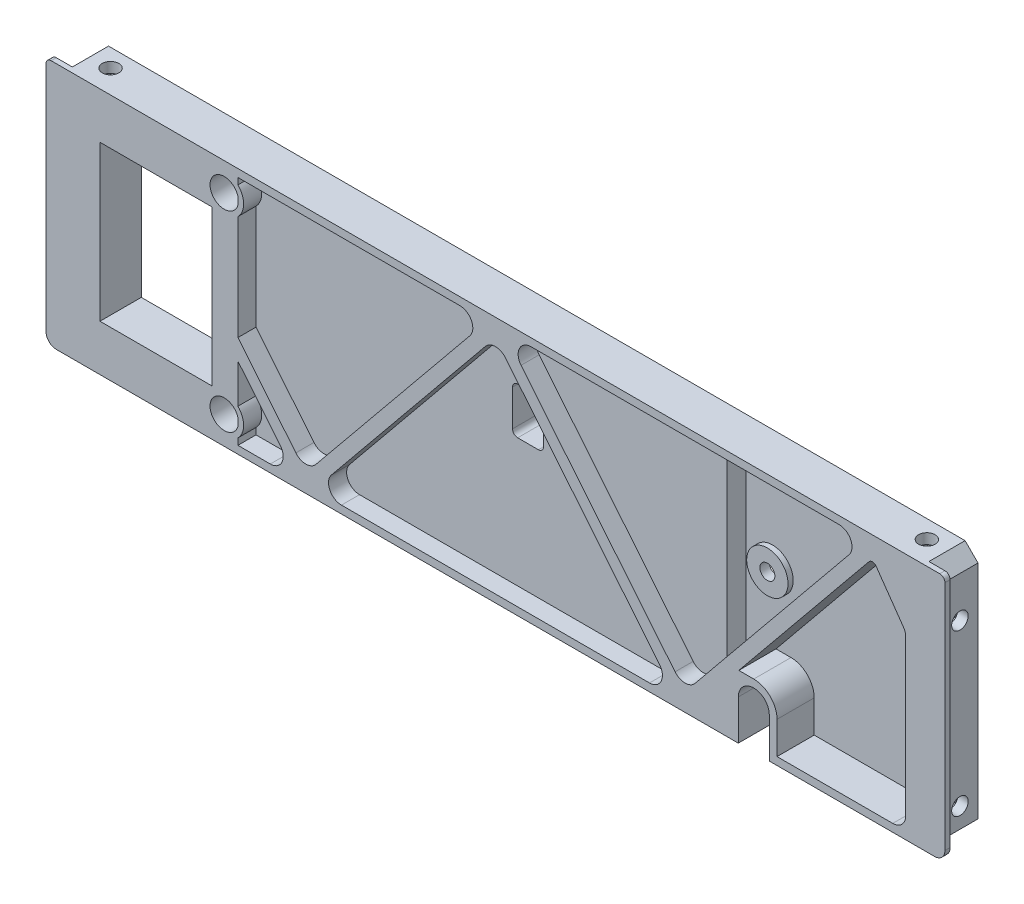
SolidWorks part; units mm, degrees
ref_plane "Front Plane" through (0, 0, 0) normal (0, 0, 1) x (1, 0, 0)
ref_plane "Top Plane" through (0, 0, 0) normal (0, 1, 0) x (1, 0, 0)
ref_plane "Right Plane" through (0, 0, 0) normal (1, 0, 0) x (0, 0, -1)
sketch "Sketch1" plane through (0, 0, 0) normal (0, 0, 1) x (1, 0, 0)
  line L1 (87, -25.55) -> (-87, -25.55)
  line L2 (87, -25.55) -> (87, 25.55)
  line L3 (87, 25.55) -> (-87, 25.55)
  line L4 (-87, -25.55) -> (-87, 25.55)
  line L5 (87, -25.55) -> (-87, 25.55) construction
  line L6 (87, 25.55) -> (-87, -25.55) construction
  point P0 (0, 0)
  dimension "D1" = 174
  dimension "D2" = 51.1
extrude "Boss-Extrude1" add sketch "Sketch1" against normal blind 8
sketch "Sketch2" plane through (0, 0, -8) normal (0, 0, -1) x (-1, 0, 0)
  line L5 (-87, -25.55) -> (-87, 25.55) construction
  line L6 (-87, 25.55) -> (87, 25.55) construction
  line L13 (85.4, -23.95) -> (85.4, 23.95)
  line L14 (-85.4, -23.95) -> (85.4, -23.95)
  line L15 (-85.4, 23.95) -> (-85.4, -23.95)
  line L16 (85.4, 23.95) -> (-85.4, 23.95)
  point P2 (0, 23.95)
  point P5 (85.4, 0)
  dimension "D1" = 1.6
  dimension "D2" = 1.6
extrude "Cut-Extrude1" cut sketch "Sketch2" against normal offset from surface (7 mm away) 1 flip side to cut up to face at (0, 0, 0)
chamfer "Chamfer1" distance 2.5 angle 45 4 edges at (-85.4, -23.95, -4.5) (-85.4, 23.95, -4.5) (85.4, -23.95, -4.5) (85.4, 23.95, -4.5)
fillet "Fillet1" radius 0.5 2 edges at (-87, 25.55, -0.5) (87, 25.55, -0.5)
sketch "Sketch3" plane through (0, 0, 0) normal (0, 0, 1) x (1, 0, 0)
  line L1 (-82.9, 23.95) -> (-85.4, 21.45) construction
  line L2 (-82.9, 23.95) -> (82.9, 23.95) construction
  line L3 (-82.9, 23.95) -> (-85.4, 21.45) construction
  line L4 (-82.9, 23.95) -> (82.9, 23.95) construction
  line L5 (85.4, 21.45) -> (82.9, 23.95) construction
  line L6 (85.4, 21.45) -> (85.4, -21.45) construction
  line L7 (82.9, -23.95) -> (85.4, -21.45) construction
  line L8 (82.9, -23.95) -> (-82.9, -23.95) construction
  line L9 (-85.4, -21.45) -> (-82.9, -23.95) construction
  line L10 (-85.4, -21.45) -> (-85.4, 21.45) construction
  line L11 (85.4, 21.45) -> (82.9, 23.95) construction
  line L12 (85.4, 21.45) -> (85.4, -21.45) construction
  line L13 (82.9, -23.95) -> (85.4, -21.45) construction
  line L14 (82.9, -23.95) -> (-82.9, -23.95) construction
  line L15 (-85.4, -21.45) -> (-82.9, -23.95) construction
  line L16 (-85.4, -21.45) -> (-85.4, 21.45) construction
  line L26 (79.4, -22.45) -> (-79.4, -22.45)
  line L27 (79.4, -22.45) -> (79.4, 22.45)
  line L28 (79.4, 22.45) -> (-79.4, 22.45)
  line L29 (-79.4, -22.45) -> (-79.4, 22.45)
  line L30 (79.4, -22.45) -> (-79.4, 22.45) construction
  line L31 (79.4, 22.45) -> (-79.4, -22.45) construction
  point P4 (0, 0)
  dimension "D1" = 3
  dimension "D2" = 6
extrude "Cut-Extrude2" cut sketch "Sketch3" against normal offset from surface (7.2 mm away) 0.8 up to face at (0, 0, -8)
sketch "Sketch9" plane through (0, 0, 0) normal (0, 0, 1) x (1, 0, 0)
  line L0 (-73.4, 22.45) -> (-73.4, 19.45)
  line L1 (-79.4, 22.45) -> (79.4, 22.45) construction
  line L2 (-73.4, 19.45) -> (-79.4, 10.8811)
  line L3 (-79.4, -22.45) -> (-79.4, 22.45) construction
  line L4 (-79.4, 10.8811) -> (-79.4, 22.45)
  line L5 (-79.4, 22.45) -> (-73.4, 22.45)
  dimension "D1" = 6
  dimension "D2" = 35
  dimension "D3" = 3
extrude "Boss-Extrude2" add sketch "Sketch9" against normal up to surface (7.2 mm away) up to face at (0, 0, -7.2)
hole_wizard "Ø3.0mm Dowel Hole1" positions "Sketch4" profile "Sketch5" hole size "Ø3.0" standard "ANSI Metric"
sketch "Sketch4" plane through (-85.4, 0, 0) normal (-1, 0, 0) x (0, 0, 1)
  line L0 (-4.5, 13.55) -> (-4.5, -17.55) construction
  line L2 (-8, -21.45) -> (-8, 21.45) construction
  line L3 (-1, 25.55) -> (0, 25.55) construction
  line L5 (-1, -25.55) -> (0, -25.55) construction
  point P0 (-4.5, 13.55)
  point P3 (-4.5, -17.55)
  point P15 (-0.5, 25.55)
  dimension "D1" = 3.5
  dimension "D2" = 12
  dimension "D3" = 8
sketch "Sketch5" plane through (-85.4, 13.55, -4.5) normal (0, 1, 0) x (0, 0, 1)
  line L0 (0, 0) -> (0, 5)
  line L1 (0, 5) -> (1.6, 5)
  line L2 (1.6, 5) -> (1.6, 0)
  line L5 (1.6, 0) -> (0, 0)
  line L10 (0, 5) -> (-1.6, 5) construction
  line L11 (0, -6.35) -> (0, 107.95) construction
  dimension "Hole Dia." = 3.2
  dimension "Hole Depth" = 5
  dimension "Drill Angle" = 180
hole_wizard "Ø3.0mm Dowel Hole2" positions "Sketch7" profile "Sketch8" hole size "Ø3.0" standard "ANSI Metric"
sketch "Sketch7" plane through (0, 23.95, 0) normal (0, 1, 0) x (1, 0, 0)
  line L0 (-82.9, 8) -> (82.9, 8) construction
  line L1 (-87, 0) -> (-87, 1) construction
  point P0 (-79, 4.5)
  dimension "D1" = 3.5
  dimension "D2" = 8
sketch "Sketch8" plane through (-79, 23.95, -4.5) normal (1, 0, 0) x (0, 0, 1)
  line L0 (0, 0) -> (0, 5)
  line L1 (0, 5) -> (1.6, 5)
  line L2 (1.6, 5) -> (1.6, 0)
  line L5 (1.6, 0) -> (0, 0)
  line L10 (0, 5) -> (-1.6, 5) construction
  line L11 (0, -6.35) -> (0, 107.95) construction
  dimension "Hole Dia." = 3.2
  dimension "Hole Depth" = 5
  dimension "Drill Angle" = 180
sketch "Sketch10" plane through (-85.4, 0, 0) normal (-1, 0, 0) x (0, 0, 1)
  line L0 (-8, -21.45) -> (-8, 21.45) construction
  line L1 (-8, 16.3) -> (-1.75, 16.3)
  line L2 (-8, 16.3) -> (-8, 10.8)
  line L3 (-8, 10.8) -> (-1.75, 10.8)
  line L4 (-1.75, 16.3) -> (-1.75, 10.8)
  line L6 (-8, -14.8) -> (-1.75, -14.8)
  line L7 (-8, -14.8) -> (-8, -20.3)
  line L8 (-8, -20.3) -> (-1.75, -20.3)
  line L9 (-1.75, -14.8) -> (-1.75, -20.3)
  point P6 (-1.75, -17.55)
  point P8 (-1.75, 13.55)
  dimension "D1" = 5.5
  dimension "D2" = 2.75
extrude "Cut-Extrude3" cut sketch "Sketch10" against normal blind 1.8 from offset 2 offset against normal yes
sketch "Sketch11" plane through (0, 23.95, 0) normal (0, 1, 0) x (1, 0, 0)
  line L0 (-82.9, 8) -> (82.9, 8) construction
  line L1 (-81.75, 8) -> (-76.25, 8)
  line L2 (-81.75, 8) -> (-81.75, 1.75)
  line L3 (-81.75, 1.75) -> (-76.25, 1.75)
  line L4 (-76.25, 8) -> (-76.25, 1.75)
  point P6 (-79, 1.75)
  dimension "D1" = 5.5
  dimension "D2" = 2.75
extrude "Cut-Extrude4" cut sketch "Sketch11" against normal blind 1.8 from offset 2 offset against normal yes
mirror "Mirror1" about plane through (0, 0, 0) normal (1, 0, 0) of "Cut-Extrude4", "Cut-Extrude3", "Ø3.0mm Dowel Hole2", "Ø3.0mm Dowel Hole1", "Boss-Extrude2"
sketch "Sketch12" plane through (0, 0, -7.2) normal (0, 0, 1) x (1, 0, 0)
  line L0 (-73.4, 22.45) -> (-36.7, -22.45) construction
  line L1 (-79.4, -22.45) -> (79.4, -22.45) construction
  line L2 (-36.7, -22.45) -> (0, 22.45) construction
  line L3 (73.4, 22.45) -> (-73.4, 22.45) construction
  line L4 (0, 22.45) -> (36.7, -22.45) construction
  line L5 (36.7, -22.45) -> (73.4, 22.45) construction
  line L6 (-74.3678, 21.6589) -> (-37.4743, -23.4779)
  line L7 (-35.9257, -23.4779) -> (0, 20.4748)
  line L8 (0, 20.4748) -> (35.9257, -23.4779)
  line L9 (37.4743, -23.4779) -> (74.3678, 21.6589)
  line L10 (-72.4322, 23.2411) -> (-36.7, -20.4748)
  line L11 (-36.7, -20.4748) -> (-0.7743, 23.4779)
  line L12 (0.7743, 23.4779) -> (36.7, -20.4748)
  line L13 (36.7, -20.4748) -> (72.4322, 23.2411)
  line L14 (0, 20.4748) -> (36.7, -24.4252) construction
  line L15 (36.7, -24.4252) -> (74.3678, 21.6589) construction
  line L16 (-36.7, -20.4748) -> (0, 24.4252) construction
  line L17 (0, 24.4252) -> (36.7, -20.4748) construction
  line L18 (-74.3678, 21.6589) -> (-36.7, -24.4252) construction
  line L19 (-36.7, -24.4252) -> (0, 20.4748) construction
  arc A0 (-74.3678, 21.6589) -> (-72.4322, 23.2411) centre (-73.4, 22.45) cw
  arc A1 (74.3678, 21.6589) -> (72.4322, 23.2411) centre (73.4, 22.45) ccw
  arc A2 (35.9257, -23.4779) -> (37.4743, -23.4779) centre (36.7, -22.845) ccw
  arc A3 (-0.7743, 23.4779) -> (0.7743, 23.4779) centre (0, 22.845) cw
  arc A4 (-37.4743, -23.4779) -> (-35.9257, -23.4779) centre (-36.7, -22.845) ccw
  dimension "D3" = 1
  dimension "D1" = 1.25
extrude "Boss-Extrude3" add sketch "Sketch12" along normal up to surface (7.2 mm away) up to face at (0, 7.5828, 0)
sketch "Sketch13" plane through (0, 0, 0) normal (0, 0, 1) x (1, 0, 0)
  line L0 (-73.4, 19.45) -> (-73.4, 20.4748)
  line L1 (-73.4, 20.4748) -> (-72.5623, 19.45)
  line L2 (-73.4, 20.4748) -> (-38.3144, -22.45) construction
  line L3 (-72.5623, 19.45) -> (-73.4, 19.45)
  line L4 (0, 0) -> (0, 25.4565) construction
  line L5 (72.5623, 19.45) -> (73.4, 19.45)
  line L6 (73.4, 20.4748) -> (72.5623, 19.45)
  line L7 (73.4, 19.45) -> (73.4, 20.4748)
extrude "Small Fix" add sketch "Sketch13" against normal up to surface (7.2 mm away) up to face at (-68.7829, 1.1812, -7.2)
sketch "Sketch14" plane through (0, 0, -1) normal (0, 0, -1) x (-1, 0, 0)
  line L0 (87, -25.55) -> (87, 25.05) construction
  line L1 (-87, -25.55) -> (87, -25.55)
  line L2 (-87, -25.55) -> (-87, -23.95)
  line L3 (-87, -23.95) -> (87, -23.95)
  line L4 (87, -25.55) -> (87, -23.95)
  line L5 (-82.9, -23.95) -> (82.9, -23.95) construction
extrude "Cut-Extrude5" cut sketch "Sketch14" against normal through all
fillet "Fillet2" radius 2.5 15 edges at (79.4, -22.45, -3.6) (79.4, 10.8811, -3.6) (38.3144, -22.45, -3.6) (71.7856, 22.45, -3.6) (36.7, -20.4748, -3.6) (1.6144, 22.45, -3.6) (35.0856, -22.45, -3.6) (0, 20.4748, -3.6) (-35.0856, -22.45, -3.6) (-1.6144, 22.45, -3.6) (-36.7, -20.4748, -3.6) (-71.7856, 22.45, -3.6) (-79.4, 10.8811, -3.6) (-79.4, -22.45, -3.6) (-38.3144, -22.45, -3.6)
fillet "Fillet3" radius 1 4 edges at (73.4, 19.45, -3.6) (72.5623, 19.45, -3.6) (-72.5623, 19.45, -3.6) (-73.4, 19.45, -3.6)
fillet "Fillet4" radius 2 2 edges at (-87, -23.95, -0.5) (87, -23.95, -0.5)
sketch "Sketch23" plane through (0, 0, -1) normal (0, 0, -1) x (-1, 0, 0)
  line L0 (82.9, 23.95) -> (-82.9, 23.95) construction
  line L1 (-87, 25.55) -> (87, 25.55)
  line L2 (-87, 25.55) -> (-87, 23.95)
  line L3 (-87, 23.95) -> (87, 23.95)
  line L4 (87, 25.55) -> (87, 23.95)
  line L5 (87, -21.95) -> (87, 25.05) construction
  line L6 (86.5, 25.55) -> (-86.5, 25.55) construction
  line L7 (-87, 25.05) -> (-87, -21.95) construction
extrude "Cut-Extrude9" cut sketch "Sketch23" against normal through all
sketch "Sketch24" plane through (0, 0, 0) normal (0, 0, 1) x (1, 0, 0)
  line L0 (79.4, -19.95) -> (79.4, 10.0929) construction
  line L1 (49.85, 22.45) -> (73.6986, 22.45) construction
  line L2 (49.85, 22.45) -> (49.85, -22.45) construction
  line L3 (49.85, -22.45) -> (79.4, -22.45) construction
  line L4 (79.4, 10.0929) -> (79.4, -22.45) construction
  line L5 (43.5867, -22.45) -> (76.9, -22.45) construction
  line L6 (66.5133, 22.45) -> (6.8867, 22.45) construction
  line L7 (78.9479, 11.5268) -> (73.6986, 19.0236) construction
  line L8 (78.9479, 11.5268) -> (73.6986, 19.0236) construction
  line L9 (73.6986, 19.0236) -> (73.6986, 22.45) construction
  line L10 (0, 23.95) -> (0, -23.95) construction
  line L11 (54.85, 15) -> (76.55, 15) construction
  line L12 (54.85, 15) -> (54.85, -15) construction
  line L13 (54.85, -15) -> (76.55, -15) construction
  line L14 (76.55, 15) -> (76.55, -15) construction
  line L15 (87, 23.95) -> (-87, 23.95) construction
  line L16 (-85, -23.95) -> (85, -23.95) construction
  line L17 (-76.55, 15) -> (-76.55, -15) construction
  line L18 (-54.85, -15) -> (-76.55, -15) construction
  line L19 (-54.85, 15) -> (-54.85, -15) construction
  line L20 (-54.85, 15) -> (-76.55, 15) construction
  line L21 (-73.6986, 19.0236) -> (-73.6986, 22.45)
  line L22 (-78.9479, 11.5268) -> (-73.6986, 19.0236)
  line L23 (-79.4, 10.0929) -> (-79.4, -22.45)
  line L24 (-49.85, -22.45) -> (-79.4, -22.45)
  line L25 (-49.85, 22.45) -> (-49.85, -22.45)
  line L26 (-49.85, 22.45) -> (-73.6986, 22.45)
  line L27 (87, -21.95) -> (87, 23.95) construction
  arc A0 (79.4, 10.0929) -> (78.9479, 11.5268) centre (76.9, 10.0929) ccw construction
  arc A1 (79.4, 10.0929) -> (78.9479, 11.5268) centre (76.9, 10.0929) ccw construction
  arc A2 (-79.4, 10.0929) -> (-78.9479, 11.5268) centre (-76.9, 10.0929) cw
  point P18 (0, 0)
  point P21 (76.55, 0)
  dimension "D1" = 10.45
  dimension "D2" = 21.7
  dimension "D3" = 30
  dimension "D4" = 5
extrude "Boss-Extrude7" add sketch "Sketch24" against normal up to surface (7.2 mm away) up to face at (36.7, 7.6215, -7.2)
sketch "Sketch26" plane through (0, 0, 0) normal (0, 0, 1) x (1, 0, 0)
  line L8 (-54.85, 15) -> (-54.85, -15) construction
  line L9 (-54.85, -15) -> (-76.55, -15) construction
  line L10 (-76.55, 15) -> (-76.55, -15) construction
  line L11 (-54.85, 15) -> (-76.55, 15) construction
  line L12 (-54.85, 15) -> (-54.85, -15)
  line L13 (-54.85, -15) -> (-76.55, -15)
  line L14 (-76.55, 15) -> (-76.55, -15)
  line L15 (-54.85, 15) -> (-76.55, 15)
extrude "Cut-Extrude10" cut sketch "Sketch26" against normal up to surface (8 mm away) up to face at (82.5, 13.55, -8)
sketch "Sketch27" plane through (0, 0, -8) normal (0, 0, -1) x (-1, 0, 0)
  line L0 (82.9, 23.95) -> (-82.9, 23.95) construction
  line L1 (2.75, 21.95) -> (45.85, 21.95) construction
  line L2 (2.75, 21.95) -> (2.75, 4.65) construction
  line L3 (2.75, 4.65) -> (45.85, 4.65) construction
  line L4 (45.85, 21.95) -> (45.85, 4.65) construction
  line L5 (18.72, -1.95) -> (45.85, -1.95) construction
  line L6 (18.72, -1.95) -> (18.72, -21.95) construction
  line L7 (18.72, -21.95) -> (45.85, -21.95) construction
  line L8 (45.85, -1.95) -> (45.85, -21.95) construction
  line L9 (-40.45, 21.95) -> (-7.75, 21.95) construction
  line L10 (-40.45, 21.95) -> (-40.45, 4.23) construction
  line L11 (-40.45, 4.23) -> (-7.75, 4.23) construction
  line L12 (-7.75, 21.95) -> (-7.75, 4.23) construction
  line L13 (-82.9, -23.95) -> (82.9, -23.95) construction
  line L15 (54.85, 15) -> (54.85, -15) construction
  line L24 (-40.28, -1.45) -> (4.72, -1.45) construction
  line L25 (-40.28, -1.45) -> (-40.28, -21.95) construction
  line L26 (-40.28, -21.95) -> (4.72, -21.95) construction
  line L27 (4.72, -1.45) -> (4.72, -21.95) construction
  dimension "D1" = 43.1
  dimension "D2" = 17.3
  dimension "D3" = 27.13
  dimension "D4" = 20
  dimension "D5" = 32.7
  dimension "D6" = 17.72
  dimension "D7" = 2
  dimension "D8" = 20.5
  dimension "D9" = 45
  dimension "D10" = 2
  dimension "D11" = 14
  dimension "D12" = 9
  dimension "D13" = 10.5
fillet "Fillet5" radius 1 2 edges at (87, 23.95, -0.5) (-87, 23.95, -0.5)
sketch "Sketch28" plane through (0, 0, -7.2) normal (0, 0, 1) x (1, 0, 0)
  line L0 (43.5867, -22.45) -> (76.9, -22.45) construction
  line L1 (-49.85, 22.45) -> (41.28, 22.45)
  line L2 (-49.85, 22.45) -> (-49.85, -22.45)
  line L3 (-49.85, -22.45) -> (41.28, -22.45)
  line L4 (41.28, 22.45) -> (41.28, -22.45)
  line L5 (40.28, -1.45) -> (40.28, -21.95) construction
  dimension "D1" = 1
extrude "Boss-Extrude8" add sketch "Sketch28" along normal blind 3.7
sketch "Sketch29" plane through (0, 0, -8) normal (0, 0, -1) x (-1, 0, 0)
  line L0 (-7.75, 21.95) -> (-7.75, 4.23) construction
  line L1 (-40.45, 4.23) -> (-7.75, 4.23) construction
  line L2 (-40.45, 21.95) -> (-40.45, 4.23) construction
  line L3 (-40.45, 21.95) -> (-7.75, 21.95) construction
  line L4 (-7.75, 21.95) -> (-7.75, 4.23) construction
  line L5 (-40.45, 4.23) -> (-7.75, 4.23) construction
  line L6 (-40.45, 21.95) -> (-40.45, 4.23) construction
  line L7 (-40.45, 21.95) -> (-7.75, 21.95) construction
  line L8 (4.72, -1.45) -> (4.72, -21.95) construction
  line L9 (-40.28, -21.95) -> (4.72, -21.95) construction
  line L10 (-40.28, -1.45) -> (-40.28, -21.95) construction
  line L11 (-40.28, -1.45) -> (4.72, -1.45) construction
  line L12 (18.72, -1.95) -> (18.72, -21.95) construction
  line L13 (18.72, -21.95) -> (45.85, -21.95) construction
  line L14 (45.85, -1.95) -> (45.85, -21.95) construction
  line L15 (18.72, -1.95) -> (45.85, -1.95) construction
  line L16 (2.75, 4.65) -> (45.85, 4.65) construction
  line L17 (45.85, 21.95) -> (45.85, 4.65) construction
  line L18 (2.75, 21.95) -> (45.85, 21.95) construction
  line L19 (2.75, 21.95) -> (2.75, 4.65) construction
  line L20 (4.72, -1.45) -> (4.72, -21.95) construction
  line L21 (-40.28, -21.95) -> (4.72, -21.95) construction
  line L22 (-40.28, -1.45) -> (-40.28, -21.95) construction
  line L23 (-40.28, -1.45) -> (4.72, -1.45) construction
  line L24 (18.72, -1.95) -> (18.72, -21.95) construction
  line L25 (18.72, -21.95) -> (45.85, -21.95) construction
  line L26 (45.85, -1.95) -> (45.85, -21.95) construction
  line L27 (18.72, -1.95) -> (45.85, -1.95) construction
  line L28 (2.75, 4.65) -> (45.85, 4.65) construction
  line L29 (45.85, 21.95) -> (45.85, 4.65) construction
  line L30 (2.75, 21.95) -> (45.85, 21.95) construction
  line L31 (2.75, 21.95) -> (2.75, 4.65) construction
  line L32 (-7.6, 22.1) -> (-7.6, 4.08)
  line L33 (-40.6, 4.08) -> (-7.6, 4.08)
  line L34 (-40.6, 22.1) -> (-40.6, 4.08)
  line L35 (-40.6, 22.1) -> (-7.6, 22.1)
  line L36 (4.87, -1.3) -> (4.87, -22.1)
  line L37 (-40.43, -22.1) -> (4.87, -22.1)
  line L38 (-40.43, -1.3) -> (-40.43, -22.1)
  line L39 (-40.43, -1.3) -> (4.87, -1.3)
  line L40 (18.57, -1.8) -> (18.57, -22.1)
  line L41 (18.57, -22.1) -> (46, -22.1)
  line L42 (46, -1.8) -> (46, -22.1)
  line L43 (18.57, -1.8) -> (46, -1.8)
  line L44 (2.6, 4.5) -> (46, 4.5)
  line L45 (46, 22.1) -> (46, 4.5)
  line L46 (2.6, 22.1) -> (46, 22.1)
  line L47 (2.6, 22.1) -> (2.6, 4.5)
  dimension "D1" = 0.15
extrude "Cut-Extrude11" cut sketch "Sketch29" against normal blind 1.6
sketch "Sketch30" plane through (0, 0, -6.4) normal (0, 0, -1) x (-1, 0, 0)
  line L0 (4.87, -1.3) -> (-40.43, -1.3) construction
  line L1 (-40.43, -1.3) -> (-26.43, -1.3)
  line L2 (-40.43, -1.3) -> (-40.43, -11.7)
  line L3 (-40.43, -11.7) -> (-26.43, -11.7)
  line L4 (-26.43, -1.3) -> (-26.43, -11.7)
  line L7 (-40.43, -1.3) -> (-40.43, -22.1) construction
  line L8 (-40.43, -22.1) -> (4.87, -22.1) construction
  line L9 (3.67, -1.3) -> (-3.13, -1.3)
  line L10 (3.67, -1.3) -> (3.67, -22.1)
  line L11 (3.67, -22.1) -> (-3.13, -22.1)
  line L12 (-3.13, -1.3) -> (-3.13, -22.1)
  line L13 (4.87, -22.1) -> (4.87, -1.3) construction
  line L14 (4.87, -22.1) -> (4.87, -1.3) construction
  line L15 (46, 22.1) -> (2.6, 22.1) construction
  line L16 (5.6, 22.1) -> (34, 22.1)
  line L17 (5.6, 22.1) -> (5.6, 4.5)
  line L18 (5.6, 4.5) -> (34, 4.5)
  line L19 (34, 22.1) -> (34, 4.5)
  line L20 (2.6, 4.5) -> (46, 4.5) construction
  line L21 (46, 22.1) -> (2.6, 22.1) construction
  line L22 (46, 4.5) -> (39, 4.5)
  line L23 (46, 4.5) -> (46, 22.1)
  line L24 (46, 22.1) -> (39, 22.1)
  line L25 (39, 4.5) -> (39, 22.1)
  line L26 (2.6, 22.1) -> (2.6, 4.5) construction
  line L27 (46, -1.8) -> (18.57, -1.8) construction
  line L29 (22.57, -1.8) -> (22.57, -22.1)
  line L31 (39.5, -1.8) -> (39.5, -22.1)
  line L32 (18.57, -22.1) -> (46, -22.1) construction
  line L33 (18.57, -1.8) -> (18.57, -22.1) construction
  line L34 (46, -22.1) -> (46, -1.8) construction
  line L36 (22.57, -1.8) -> (18.57, -1.8)
  line L37 (18.57, -1.8) -> (18.57, -22.1)
  line L38 (18.57, -22.1) -> (22.57, -22.1)
  line L39 (39.5, -22.1) -> (46, -22.1)
  line L40 (46, -22.1) -> (46, -1.8)
  line L41 (46, -1.8) -> (39.5, -1.8)
  point P11 (-40.43, -11.7)
  dimension "D1" = 14
  dimension "D2" = 1.2
  dimension "D3" = 8
  dimension "D4" = 7
  dimension "D5" = 12
  dimension "D6" = 3
  dimension "D7" = 4
  dimension "D8" = 6.5
extrude "Cut-Extrude12" cut sketch "Sketch30" against normal offset from surface (2.4 mm away) 0.5 up to face at (27.7511, 1.9795, -3.5)
sketch "Sketch31" plane through (0, 0, -3.5) normal (0, 0, 1) x (1, 0, 0)
  circle A0 centre (46.43, 1.39) radius 1.45 construction
  circle A1 centre (-52.5, -18.55) radius 1.45 construction
  circle A2 centre (-52.5, 18.55) radius 1.45 construction
  circle A3 centre (46.43, 1.39) radius 1.45
  circle A4 centre (-52.5, -18.55) radius 1.45
  circle A5 centre (-52.5, 18.55) radius 1.45
extrude "Cut-Extrude13" cut sketch "Sketch31" against normal through all both and the other way through all
sketch "Sketch32" plane through (0, 0, 0) normal (0, 0, 1) x (1, 0, 0)
  circle A0 centre (-52.5, 18.55) radius 2.75
  circle A1 centre (-52.5, -18.55) radius 2.75
  dimension "D1" = 5.5
extrude "Cut-Extrude14" cut sketch "Sketch32" against normal offset from surface (6 mm away) 2 up to face at (47.88, 1.39, -8)
sketch "Sketch33" plane through (0, 0, -7.2) normal (0, 0, 1) x (1, 0, 0)
  circle A0 centre (46.43, 1.39) radius 4
  circle A1 centre (46.43, 1.39) radius 1.45 construction
  circle A2 centre (46.43, 1.39) radius 1.45
  dimension "D1" = 8
extrude "Boss-Extrude9" add sketch "Sketch33" along normal blind 1
sketch "Sketch34" plane through (0, 0, 0) normal (0, 0, 1) x (1, 0, 0)
  line L0 (-49.85, 21.2033) -> (-49.85, 15.8967)
  line L1 (-49.85, 22.45) -> (-49.85, 19.2848) construction
  line L2 (-27.7429, 0) -> (-42.669, 0) construction
  line L3 (-49.85, -21.2033) -> (-49.85, -15.8967)
  arc A0 (-49.85, 15.8967) -> (-49.85, 21.2033) centre (-52.5, 18.55) ccw
  arc A1 (-49.85, -15.8967) -> (-49.85, -21.2033) centre (-52.5, -18.55) cw
  dimension "D1" = 3.75
extrude "Boss-Extrude10" add sketch "Sketch34" against normal up to surface (3.5 mm away) up to face at (-35.4058, 7.4328, -3.5)
sketch "Sketch35" plane through (0, 0, -7.2) normal (0, 0, 1) x (1, 0, 0)
  line L0 (47, -16.2) -> (47, -23.95)
  line L4 (-85, -23.95) -> (85, -23.95) construction
  line L5 (53, -16.2) -> (53, -23.95)
  line L6 (53, -23.95) -> (47, -23.95)
  line L7 (50, -23.95) -> (50, -16.2) construction
  line L9 (87, -21.95) -> (87, 22.95) construction
  circle A4 centre (50, -16.2) radius 2.2 construction
  arc A5 (47, -16.2) -> (53, -16.2) centre (50, -16.2) cw
  point P4 (50, -23.95)
  dimension "D2" = 4.4
  dimension "D3" = 6
  dimension "D1" = 7.75
  dimension "D4" = 37
extrude "Cut-Extrude15" cut sketch "Sketch35" against normal through all both and the other way through all
sketch "Sketch37" plane through (0, 0, 0) normal (0, 0, 1) x (1, 0, 0)
  line L6 (47, -16.2) -> (47, -22.45) construction
  line L7 (53, -22.45) -> (53, -16.2) construction
  line L8 (47, -16.2) -> (47, -22.45)
  line L9 (53, -22.45) -> (53, -16.2)
  line L10 (50, -11.7) -> (47.1012, -11.7)
  line L11 (41.6511, -18.3678) -> (72.2622, 19.0829) construction
  line L12 (41.6511, -18.3678) -> (47.1012, -11.7)
  line L13 (54.5, -22.45) -> (54.5, -16.2)
  line L14 (53, -22.45) -> (54.5, -22.45)
  line L16 (47, -22.45) -> (43.5867, -22.45) construction
  line L17 (47, -22.45) -> (43.5867, -22.45)
  line L18 (41.6511, -18.3678) -> (72.2622, 19.0829) construction
  arc A4 (53, -16.2) -> (47, -16.2) centre (50, -16.2) ccw construction
  arc A5 (53, -16.2) -> (47, -16.2) centre (50, -16.2) ccw
  arc A6 (54.5, -16.2) -> (50, -11.7) centre (50, -16.2) ccw
  arc A7 (41.6511, -18.3678) -> (43.5867, -22.45) centre (43.5867, -19.95) ccw construction
  arc A8 (54.5, -16.2) -> (45.5, -16.2) centre (50, -16.2) ccw construction
  arc A9 (41.6511, -18.3678) -> (43.5867, -22.45) centre (43.5867, -19.95) ccw
  dimension "D1" = 1.5
extrude "Boss-Extrude12" add sketch "Sketch37" against normal up to surface (7.2 mm away) up to face at (60.1165, -7.9273, -7.2)
sketch "Sketch39" plane through (0, 0, -8) normal (0, 0, -1) x (-1, 0, 0)
  line L0 (-0.8, 11.39) -> (-4.8, 11.39) construction
  line L1 (-0.8, 11.39) -> (-4.8, 11.39)
  line L2 (0.2, 3.39) -> (0.2, 10.39) construction
  line L3 (-5.8, 10.39) -> (-5.8, 3.39) construction
  line L4 (0.2, 3.39) -> (0.2, 10.39)
  line L5 (-5.8, 10.39) -> (-5.8, 3.39)
  line L6 (-4.8, 2.39) -> (-0.8, 2.39)
  arc A0 (0.2, 10.39) -> (-0.8, 11.39) centre (-0.8, 10.39) ccw construction
  arc A1 (-4.8, 11.39) -> (-5.8, 10.39) centre (-4.8, 10.39) ccw construction
  arc A2 (0.2, 10.39) -> (-0.8, 11.39) centre (-0.8, 10.39) ccw
  arc A3 (-4.8, 11.39) -> (-5.8, 10.39) centre (-4.8, 10.39) ccw
  arc A4 (-5.8, 3.39) -> (-4.8, 2.39) centre (-4.8, 3.39) ccw construction
  arc A5 (-0.8, 2.39) -> (0.2, 3.39) centre (-0.8, 3.39) ccw construction
  arc A6 (-5.8, 3.39) -> (-4.8, 2.39) centre (-4.8, 3.39) ccw
  arc A7 (-0.8, 2.39) -> (0.2, 3.39) centre (-0.8, 3.39) ccw
extrude "Cut-Extrude16" cut sketch "Sketch39" against normal through all
sketch "Sketch40" plane through (0, 0, -6.4) normal (0, 0, -1) x (-1, 0, 0)
  line L0 (-40.43, -11.7) -> (-40.43, -22.1) construction
  line L1 (-40.43, -22.1) -> (-3.13, -22.1) construction
  line L2 (-3.13, -1.3) -> (-3.13, -22.1) construction
  line L3 (-3.13, -1.3) -> (-26.43, -1.3) construction
  line L4 (-26.43, -11.7) -> (-26.43, -1.3) construction
  line L5 (-40.43, -11.7) -> (-26.43, -11.7) construction
  line L6 (-40.43, -11.7) -> (-40.43, -22.1)
  line L7 (-40.43, -22.1) -> (-3.13, -22.1)
  line L8 (-3.13, -1.3) -> (-3.13, -22.1)
  line L9 (-3.13, -1.3) -> (-26.43, -1.3)
  line L10 (-26.43, -11.7) -> (-26.43, -1.3)
  line L11 (-40.43, -11.7) -> (-26.43, -11.7)
  line L13 (3.67, -1.3) -> (4.87, -1.3)
  line L14 (3.67, -1.3) -> (3.67, -22.1)
  line L15 (3.67, -22.1) -> (4.87, -22.1)
  line L16 (4.87, -1.3) -> (4.87, -22.1)
extrude "Boss-Extrude13" add sketch "Sketch40" along normal offset from surface (0.6 mm away) 1 up to face at (2.8, 6.89, -8)
